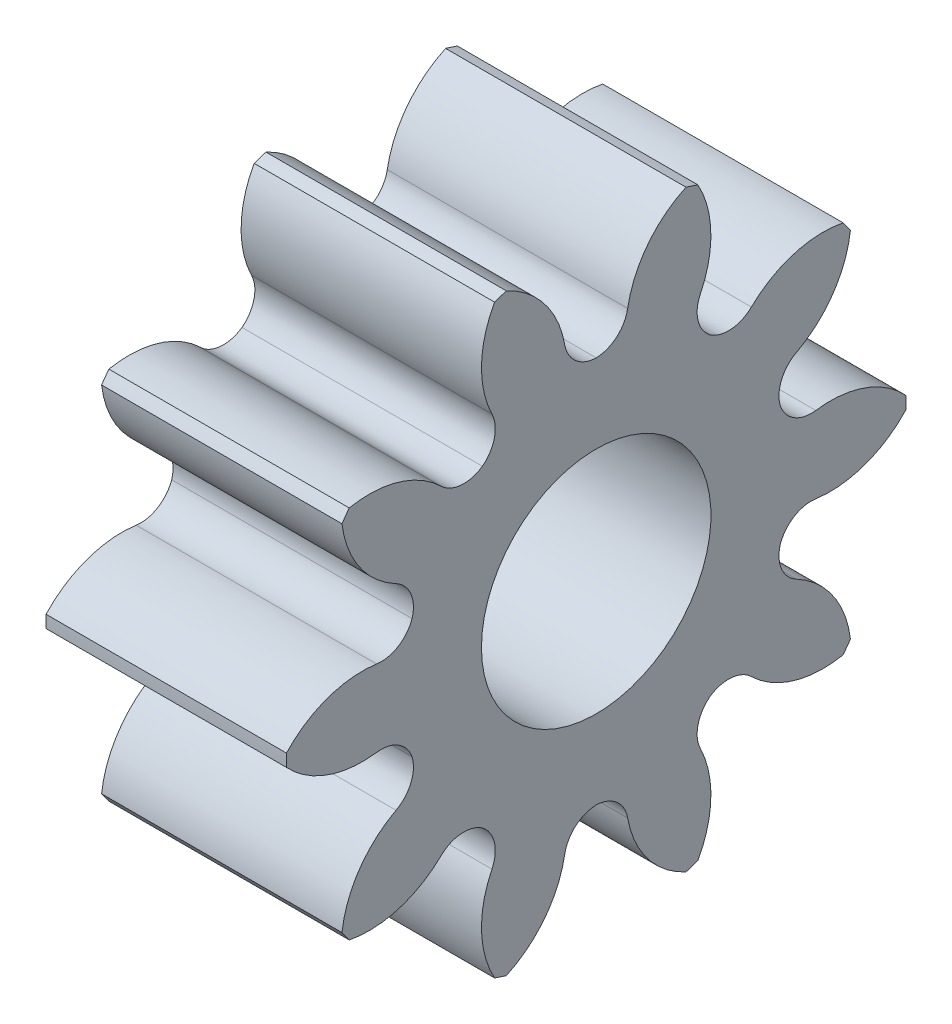
SolidWorks part; units mm, degrees
ref_plane "Plane1" through (0, 0, 0) normal (0, 0, 1) x (1, 0, 0)
ref_plane "Plane2" through (0, 0, 0) normal (0, 1, 0) x (1, 0, 0)
ref_plane "Plane3" through (0, 0, 0) normal (1, 0, 0) x (0, 0, -1)
sketch "HoldingSke" plane through (0, 0, 0) normal (0, 1, 0) x (1, 0, 0)
  line L0 (0, 0) -> (0.8754, -0.1544)
  line L1 (-15, 0) -> (100, 0) construction
  line L2 (0, 0) -> (-2.1039, 2.3779)
  line L3 (0, 0) -> (-11.863, 4.5341)
  line L4 (0, 0) -> (8.5048, 1.4996)
  line L5 (0, 0) -> (-46.8476, -17.4728)
  line L6 (0, 0) -> (-8.2896, -5.593)
  line L7 (-2.1039, 2.3779) -> (8.6586, 51.2059)
  line L8 (-76.2, 54.61) -> (-75.3, 54.61)
  line L9 (-71.009, 38.7566) -> (-53.1078, 45.2721)
  line L10 (-76.2, 71.12) -> (104.1128, 71.12)
  line L11 (0, 0) -> (-10, 0)
  line L12 (-76.2, 101.6) -> (-76.158, 101.6)
  line L13 (24.9733, 27.94) -> (52.9518, 28.4284)
  line L14 (24.9733, 27.94) -> (24.9743, 27.94)
  line L15 (24.9733, 27.94) -> (100.4006, 29.5858)
  line L16 (-63.627, -1.125) -> (-12.827, -1.125)
  circle A0 centre (0, 0) radius 2.5
  circle A1 centre (0, 0) radius 4.2177
  circle A2 centre (0, 0) radius 37.5
  circle A3 centre (0, 0) radius 2.5
  dimension "Num_teeth" = 10
  dimension "Pitch_radius" = 180.3128
  dimension "Width" = 10
  dimension "Thickness" = 10
sketch "BasProSke" plane through (0, 0, 0) normal (0, 1, 0) x (1, 0, 0)
  line L0 (-10, 0) -> (60, 0) construction
  line L1 (0, 0) -> (0, 6.75)
  line L2 (0, 0) -> (10, 0)
  line L3 (10, 0) -> (10, 6.75)
  line L4 (10, 6.75) -> (0, 6.75)
  dimension "Thickness" = 10
  dimension "Diameter" = 13.5
revolve "Base-Revolve" add sketch "BasProSke" angle 360 about L0
sketch "TooCutSke" plane through (0, 0, 0) normal (1, 0, 0) x (0, 0, -1)
  line L1 (0, 0) -> (0, 107) construction
  line L2 (0, 0) -> (-0.9533, 5.5436) construction
  line L3 (0, 0) -> (-3.4405, 10.5889) construction
  line L4 (-0.9533, 5.5436) -> (-1.7203, 5.2944) construction
  arc A0 (0.6659, 4.1649) -> (-0.6659, 4.1649) centre (0, 0) ccw
  arc A1 (1.9918, 6.476) -> (-1.9918, 6.476) centre (0, 0) ccw
  circle A2 centre (0, 0) radius 5.625 construction
  circle A3 centre (0, 0) radius 5.2858 construction
  arc A4 (-0.6659, 4.1649) -> (-1.9918, 6.476) centre (-2.9016, 4.4182) ccw
  arc A5 (1.9918, 6.476) -> (0.6659, 4.1649) centre (2.9016, 4.4182) ccw
extrude "ToothCut" cut sketch "TooCutSke" along normal through all
fillet "Breaks" [suppressed] radius 0.0225 tangent propagation no
fillet "RootFillets" [suppressed] radius 0.2823
pattern_circular "TeethCuts" count 10 every 36 about axis through (-10, 0, 0) along (1, 0, 0) of "ToothCut", "RootFillets", "Breaks"
sketch "HubNeaOneSke" plane through (0, 0, 0) normal (-1, 0, 0) x (0, 0, 1)
  circle A0 centre (0, 0) radius 4.2177
  dimension "Diameter" = 8.4355
extrude "HubNearOne" [suppressed] add sketch "HubNeaOneSke" along normal blind 40.0001
sketch "HubNeaBotSke" plane through (0, 0, 0) normal (-1, 0, 0) x (0, 0, 1)
  circle A0 centre (0, 0) radius 4.2177
  dimension "Diameter" = 8.4355
extrude "HubNearBoth" [suppressed] add sketch "HubNeaBotSke" along normal blind 20
ref_plane "FarPln" through (10, 0, 0) normal (1, 0, 0) x (0, 0, -1)
sketch "HubFarSke" plane through (10, 0, 0) normal (1, 0, 0) x (0, 0, -1)
  circle A0 centre (0, 0) radius 4.2177
  dimension "Diameter" = 8.4355
extrude "HubFar" [suppressed] add sketch "HubFarSke" along normal blind 20
sketch "BorSke" plane through (0, 0, 0) normal (1, 0, 0) x (0, 0, -1)
  circle A0 centre (0, 0) radius 2.5
  dimension "Diameter" = 5
extrude "Bore" cut sketch "BorSke" along normal mid plane 100.0001
sketch "KeySke" plane through (0, 0, 0) normal (1, 0, 0) x (0, 0, -1)
  line L0 (-1, 0) -> (-1, 3.4)
  line L1 (-1, 3.4) -> (1, 3.4)
  line L2 (1, 3.4) -> (1, 0)
  line L3 (0, 0) -> (0, 34) construction
  line L4 (-1, 0) -> (1, 0)
  dimension "Width" = 2
extrude "Keyway" [suppressed] cut sketch "KeySke" along normal mid plane 100.0001
pattern_circular "Keyway2" [suppressed] count 2 every 90 about axis through (-10, 0, 0) along (1, 0, 0) reverse direction yes
scale "Scale1" scale about centroid uniform scaling yes scale factor 1.05
fillet "Fillet1" radius 0.75 20 edges at (5, 3.1269, -3.1361) (5, 3.9489, -2.0048) (5, 2.0163, -3.943) (5, 0.6864, -4.3751) (5, -0.6864, -4.3751) (5, -2.0163, -3.943) (5, -3.1269, -3.1361) (5, -3.9489, -2.0048) (5, -4.3731, -0.6992) (5, -4.3731, 0.6992) (5, -3.9489, 2.0048) (5, -3.1269, 3.1361) (5, -2.0163, 3.943) (5, -0.6864, 4.3751) (5, 0.6864, 4.3751) (5, 2.0163, 3.943) (5, 3.9489, 2.0048) (5, 3.1269, 3.1361) (5, 4.3731, -0.6992) (5, 4.3731, 0.6992)
sketch "Sketch1" plane through (10.25, 0, 0) normal (1, 0, 0) x (0, 0, -1)
  circle A0 centre (0, 0) radius 10.2658
extrude "Cut-Extrude1" cut sketch "Sketch1" along normal blind 5 from surface starting at face at (-0.25, 0, -2.625)
equation "' \"Module@HoldingSke\" = 6.35"
equation "' \"Num_teeth@HoldingSke\" = 12"
equation "' \"Ap@HoldingSke\" =  20"
equation "' \"Ap@HoldingSke\" = 20"
equation "' \"Width@HoldingSke\" = 0.5 * 25.4"
equation "' \"Hub_dia@HoldingSke\"= 1 * 25.4"
equation "' \"Hub_dia@HoldingSke\" = 1 * 25.4"
equation "' \"Overall_len@HoldingSke\" = 1.0 * 25.4"
equation "' \"Bore@HoldingSke\" = 0.75 * 25.4"
equation "' \"T_dim@HoldingSke\" = 0.1 * 25.4"
equation "' \"Width@KeySke\" = 0.25 * 25.4"
equation "' \"Show_teeth@HoldingSke\" = 13"
equation "' \"Backlash@HoldingSke\" = 0.009 * 25.4"
equation "' \"Addendum_fac@HoldingSke\" = 1.0"
equation "' \"Dedendum_fac@HoldingSke\" = 1.25"
equation "' \"Dedendum_add@HoldingSke\" = 0.00005 * 25.4"
equation "' \"Clearance_fac@HoldingSke\" = 0.25"
equation "\"Pitch@HoldingSke\" = 1 / \"Module@HoldingSke\""
equation "\"Overcut_dia@TooCutSke\" = (\"Num_teeth@HoldingSke\" + 2 * \"Addendum_fac@HoldingSke\") / \"Pitch@HoldingSke\" + 0.002 * 25.4"
equation "\"Pitch_dia@TooCutSke\" = \"Num_teeth@HoldingSke\" / \"Pitch@HoldingSke\""
equation "\"Base_dia@TooCutSke\" = \"Num_teeth@HoldingSke\" / \"Pitch@HoldingSke\" * cos((\"Ap@HoldingSke\"  * 3.14159265 / 180))"
equation "\"Root_dia@TooCutSke\" = (\"Num_teeth@HoldingSke\" + 2) / \"Pitch@HoldingSke\" - 2 * (\"Addendum_fac@HoldingSke\" + \"Dedendum_fac@HoldingSke\") / \"Pitch@HoldingSke\" - \"Dedendum_add@HoldingSke\" * 2"
equation "\"Half_ang@TooCutSke\" = 180 / \"Num_teeth@HoldingSke\""
equation "\"Half_CT@TooCutSke\" = \"Num_teeth@HoldingSke\" / \"Pitch@HoldingSke\" * sin((3.14159265 / 2 / \"Num_teeth@HoldingSke\")) / 2 - 7 * \"Backlash@HoldingSke\" / 4"
equation "\"Flank_rad@TooCutSke\" = \"Num_teeth@HoldingSke\" / \"Pitch@HoldingSke\" / 5"
equation "\"Radius@RootFillets\" = \"Clearance_fac@HoldingSke\" / \"Pitch@HoldingSke\" + \"Dedendum_add@HoldingSke\""
equation "\"Break_rad@Breaks\" = 0.02 / \"Pitch@HoldingSke\""
equation "\"Thickness@HoldingSke\" = \"Width@HoldingSke\""
equation "\"OAL@HoldingSke\" = \"Thickness@HoldingSke\""
equation "\"MHD@HoldingSke\" = (\"Num_teeth@HoldingSke\" + 2) / \"Pitch@HoldingSke\" - 2 * (\"Addendum_fac@HoldingSke\" + \"Dedendum_fac@HoldingSke\")  / \"Pitch@HoldingSke\" - \"Dedendum_add@HoldingSke\" * 2"
equation "\"MBD@HoldingSke\" = (\"Num_teeth@HoldingSke\" + 2) / \"Pitch@HoldingSke\" - 2 * (\"Addendum_fac@HoldingSke\" + \"Dedendum_fac@HoldingSke\")  / \"Pitch@HoldingSke\" - \"Dedendum_add@HoldingSke\" * 2 - 0.002 * 25.4"
equation "\"MHD@HoldingSke\" = ((sgn( \"MHD@HoldingSke\" - \"Hub_dia@HoldingSke\" )-1)*( \"MHD@HoldingSke\" - \"Hub_dia@HoldingSke\" ))/-2+ \"Hub_dia@HoldingSke\""
equation "\"MBD@HoldingSke\" = ((sgn( \"MBD@HoldingSke\" - \"Bore@HoldingSke\" )-1)*( \"MBD@HoldingSke\" - \"Bore@HoldingSke\" ))/-2+ \"Bore@HoldingSke\""
equation "\"OAL@HoldingSke\" = ((sgn( \"OAL@HoldingSke\" - \"Overall_len@HoldingSke\" )+1)*( \"OAL@HoldingSke\" - \"Overall_len@HoldingSke\" ))/2 + \"Overall_len@HoldingSke\" + 0.000002 * 25.4"
equation "\"Num_teeth@TeethCuts\" = int( \"Show_teeth@HoldingSke\" ) + 1"
equation "\"Num_teeth@TeethCuts\" = ((sgn( \"Num_teeth@TeethCuts\" - \"Num_teeth@HoldingSke\" )-1)*( \"Num_teeth@TeethCuts\" - \"Num_teeth@HoldingSke\" ))/-2+ \"Num_teeth@HoldingSke\""
equation "\"Num_teeth@TeethCuts\" = ((sgn( \"Num_teeth@TeethCuts\" - 2.0)+1)*( \"Num_teeth@TeethCuts\" - 2.0))/2 +2.0"
equation "\"Angle@TeethCuts\" = 360.0 / \"Num_teeth@HoldingSke\""
equation "\"Diameter@BasProSke\" = (\"Num_teeth@HoldingSke\" + 2 * \"Addendum_fac@HoldingSke\") / \"Pitch@HoldingSke\""
equation "\"Thickness@BasProSke\"  = \"Thickness@HoldingSke\""
equation "' \"Fillet_rad@BasProSke\" =  \"Thickness@HoldingSke\" * 0.05"
equation "' \"Fillet_rad@BasProSke\" = \"Thickness@HoldingSke\" * 0.05"
equation "\"MHD@HoldingSke\" = ((sgn( \"MHD@HoldingSke\" - \"Root_dia@TooCutSke\" )-1)*( \"MHD@HoldingSke\" - \"Root_dia@TooCutSke\" ))/-2+ \"Root_dia@TooCutSke\""
equation "\"Diameter@HubNeaOneSke\" = \"MHD@HoldingSke\""
equation "\"Length@HubNearOne\" = \"OAL@HoldingSke\" - \"Thickness@BasProSke\""
equation "\"Diameter@HubNeaBotSke\" = \"MHD@HoldingSke\""
equation "\"Length@HubNearBoth\" = ( \"OAL@HoldingSke\" - \"Thickness@BasProSke\" ) / 2.0"
equation "\"Thickness@FarPln\" = \"Thickness@BasProSke\""
equation "\"Diameter@HubFarSke\" = \"MHD@HoldingSke\""
equation "\"Length@HubFar\" = ( \"OAL@HoldingSke\" - \"Thickness@BasProSke\" ) / 2.0"
equation "\"Diameter@BorSke\" = \"MBD@HoldingSke\""
equation "\"D1@Bore\" = \"OAL@HoldingSke\" * 2.0"
equation "\"D1@Keyway\" = \"OAL@HoldingSke\" * 2.0"
equation "\"Offset@KeySke\" = \"T_dim@HoldingSke\" + \"MBD@HoldingSke\" / 2.0"
